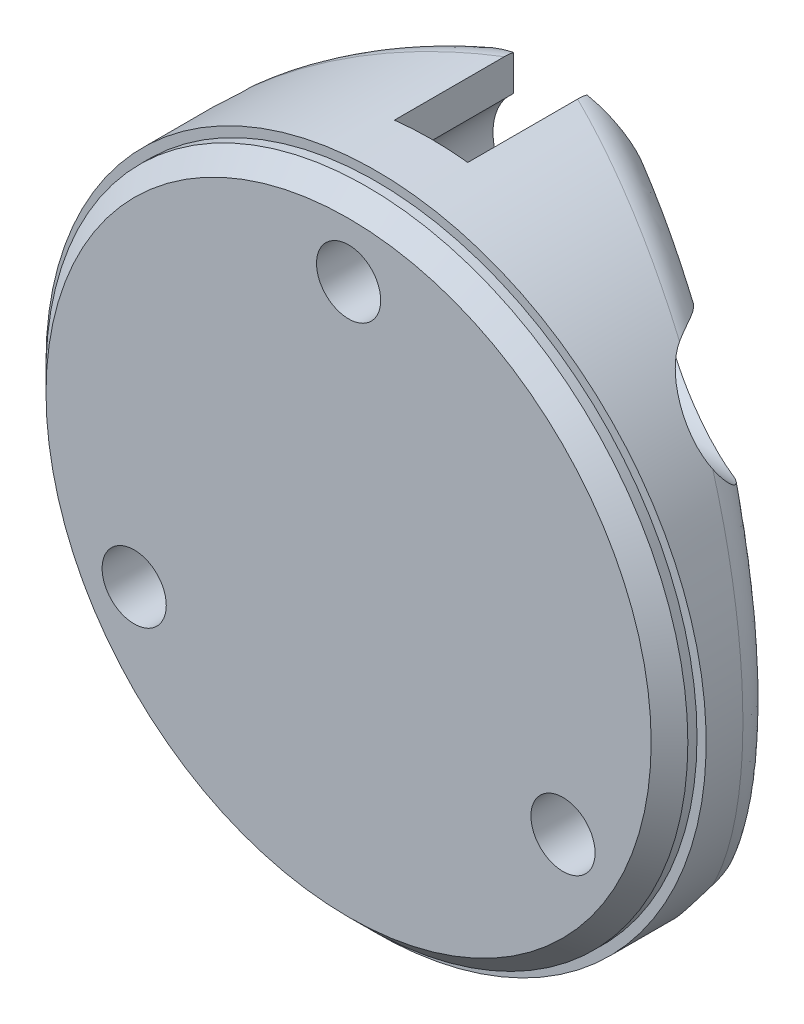
SolidWorks part; units mm, degrees
ref_plane "Front Plane" through (0, 0, 0) normal (0, 0, 1) x (1, 0, 0)
ref_plane "Top Plane" through (0, 0, 0) normal (0, 1, 0) x (1, 0, 0)
ref_plane "Right Plane" through (0, 0, 0) normal (1, 0, 0) x (0, 0, -1)
sketch "Sketch1" plane through (0, 0, 0) normal (0, 0, 1) x (1, 0, 0)
  circle A0 centre (0, 0) radius 17.5
  dimension "D1" = 35
extrude "Boss-Extrude1" add sketch "Sketch1" along normal blind 1.5
sketch "Sketch2" plane through (0, 0, 0) normal (0, 0, -1) x (-1, 0, 0)
  circle A0 centre (0, 0) radius 18
  dimension "D1" = 36
extrude "Boss-Extrude2" add sketch "Sketch2" along normal blind 3
chamfer "Chamfer1" distance 1 angle 45 1 edges at (17.5, 0, 1.5)
sketch "Sketch3" plane through (0, 0, 0) normal (0, 1, 0) x (1, 0, 0)
  line L0 (0, 0) -> (0, 9.5) construction
  line L1 (-18.5, 3) -> (-5.274, 9.5)
  line L2 (-5.274, 9.5) -> (-2, 9.5)
  line L3 (-2, 9.5) -> (-2, 3)
  line L4 (18, 3) -> (-18, 3) construction
  line L5 (-18.5, 3) -> (-2, 3)
  line L6 (18.5, 3) -> (2, 3)
  line L7 (2, 9.5) -> (2, 3)
  line L8 (5.274, 9.5) -> (2, 9.5)
  line L9 (18.5, 3) -> (5.274, 9.5)
  line L10 (18, 3) -> (-18, 3) construction
  dimension "D1" = 4
  dimension "D2" = 6.5
extrude "Boss-Extrude3" add sketch "Sketch3" along normal mid plane 40
sketch "Sketch4" plane through (0, 0, 0) normal (1, 0, 0) x (0, 0, -1)
  line L0 (5.75, 11) -> (5.75, -11) construction
  line L1 (9.5, 20) -> (9.5, -20) construction
  circle A0 centre (5.75, 11) radius 1.5
  circle A1 centre (5.75, -11) radius 1.5
  point P4 (5.75, 0)
  dimension "D1" = 3
  dimension "D2" = 22
  dimension "D3" = 3.75
extrude "Cut-Extrude1" cut sketch "Sketch4" against normal through all both and the other way through all
sketch "Sketch6" plane through (0, 0, 1.5) normal (0, 0, 1) x (1, 0, 0)
  line L1 (23.3622, -22.945) -> (-23.3622, -22.945)
  line L2 (23.3622, -22.945) -> (23.3622, 22.945)
  line L3 (23.3622, 22.945) -> (-23.3622, 22.945)
  line L4 (-23.3622, -22.945) -> (-23.3622, 22.945)
  line L5 (23.3622, -22.945) -> (-23.3622, 22.945) construction
  line L6 (23.3622, 22.945) -> (-23.3622, -22.945) construction
  circle A0 centre (0, 0) radius 18
  arc A1 (2, -17.8885) -> (2, 17.8885) centre (0, 0) ccw construction
extrude "Cut-Extrude2" cut sketch "Sketch6" against normal through all both and the other way through all
sketch "Sketch7" plane through (0, 0, -3) normal (0, 0, -1) x (-1, 0, 0)
  line L0 (2, 17.8885) -> (2, -17.8885) construction
  line L1 (-2, 7) -> (2, 7)
  line L2 (-2, 7) -> (-2, -7)
  line L3 (-2, -7) -> (2, -7)
  line L4 (2, 7) -> (2, -7)
  line L5 (-2, 7) -> (2, -7) construction
  line L6 (-2, -7) -> (2, 7) construction
  point P0 (0, 0)
  dimension "D1" = 14
extrude "Cut-Extrude3" cut sketch "Sketch7" against normal blind 3
sketch "Sketch8" plane through (0, 0, 0) normal (1, 0, 0) x (0, 0, -1)
  circle A0 centre (5.75, 11) radius 2.75
  circle A1 centre (5.75, -11) radius 2.75
  dimension "D1" = 5.5
extrude "Cut-Extrude4" cut sketch "Sketch8" along normal blind 33 from offset 6
sketch "Sketch9" plane through (0, 0, 0) normal (1, 0, 0) x (0, 0, -1)
  line L1 (7.3377, 8.25) -> (8.9254, 11)
  line L2 (8.9254, 11) -> (7.3377, 13.75)
  line L3 (7.3377, 13.75) -> (4.1623, 13.75)
  line L4 (4.1623, 13.75) -> (2.5746, 11)
  line L5 (2.5746, 11) -> (4.1623, 8.25)
  line L6 (4.1623, 8.25) -> (7.3377, 8.25)
  line L7 (4.1623, -13.75) -> (7.3377, -13.75)
  line L8 (7.3377, -13.75) -> (8.9254, -11)
  line L9 (8.9254, -11) -> (7.3377, -8.25)
  line L10 (7.3377, -8.25) -> (4.1623, -8.25)
  line L11 (4.1623, -8.25) -> (2.5746, -11)
  line L12 (2.5746, -11) -> (4.1623, -13.75)
  circle A0 centre (5.75, 11) radius 2.75 construction
  circle A1 centre (5.75, -11) radius 2.75 construction
  dimension "D1" = 5.5
extrude "Cut-Extrude5" cut sketch "Sketch9" against normal blind 33 from offset 5 offset against normal yes
fillet "Fillet1" radius 2 6 edges at (8.6647, 15.7773, -7.8336) (18, 0, -3.2457) (8.6647, -15.7773, -7.8336) (-8.6205, -15.8015, -7.8553) (-8.6205, 15.8015, -7.8553) (-18, 0, -3.2457)
sketch "Sketch10" plane through (0, 0, 1.5) normal (0, 0, 1) x (1, 0, 0)
  line L0 (-11.6913, -6.75) -> (0, 13.5) construction
  line L1 (0, 13.5) -> (11.6913, -6.75) construction
  line L2 (11.6913, -6.75) -> (-11.6913, -6.75) construction
  circle A0 centre (0, 0) radius 13.5 construction
  circle A1 centre (-11.6913, -6.75) radius 1.75
  circle A2 centre (0, 13.5) radius 1.75
  circle A3 centre (11.6913, -6.75) radius 1.75
  dimension "D1" = 27
  dimension "D2" = 3.5
extrude "Cut-Extrude6" cut sketch "Sketch10" against normal through all
sketch "Sketch12" plane through (0, 0, -9.5) normal (0, 0, -1) x (-1, 0, 0)
  circle A0 centre (0, 13.5) radius 3.125
  circle A1 centre (11.6913, -6.75) radius 3.125
  circle A2 centre (-11.6913, -6.75) radius 3.125
  dimension "D1" = 6.25
extrude "Cut-Extrude7" cut sketch "Sketch12" against normal blind 6
